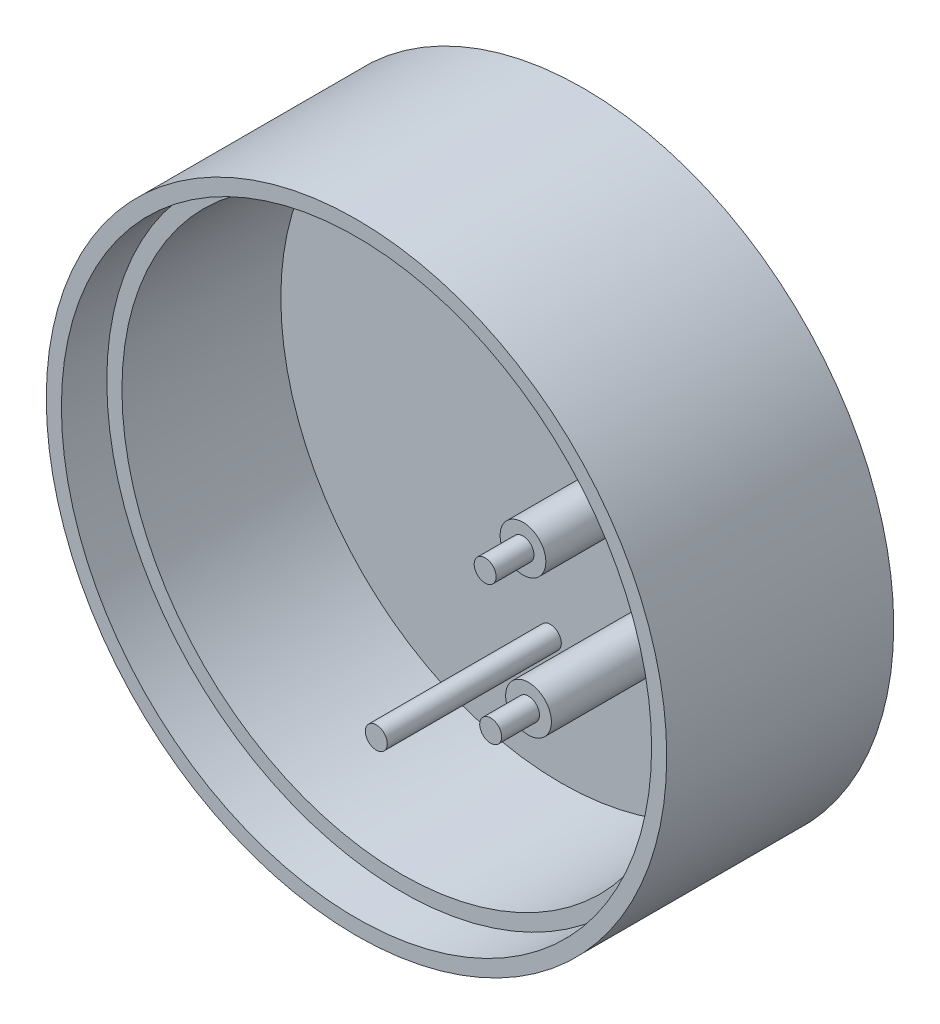
SolidWorks part; units mm, degrees
ref_plane "前视基准面" through (0, 0, 0) normal (0, 0, 1) x (1, 0, 0)
ref_plane "上视基准面" through (0, 0, 0) normal (0, 1, 0) x (1, 0, 0)
ref_plane "右视基准面" through (0, 0, 0) normal (1, 0, 0) x (0, 0, -1)
sketch "草图1" plane through (0, 0, 0) normal (0, 0, 1) x (1, 0, 0)
  circle A0 centre (0, 0) radius 41
  circle A1 centre (0, 0) radius 39
  dimension "D1" = 82
  dimension "D2" = 78
extrude "凸台-拉伸1" add sketch "草图1" along normal blind 30 contours A0 A1 region at (-39.8403, 0, 0)
sketch "草图2" plane through (0, 0, 0) normal (0, 0, 1) x (1, 0, 0)
  circle A0 centre (0, 0) radius 37
  circle A1 centre (0, 0) radius 39
  dimension "D1" = 74
  dimension "D2" = 78
extrude "凸台-拉伸2" add sketch "草图2" along normal blind 24 contours A0 | A1
sketch "草图4" plane through (0, 0, 0) normal (1, 0, 0) x (0, 0, -1)
  line L0 (-107.3488, 0) -> (127.1213, 0) construction
sketch3d "3D草图1"
  circle A1 centre (0, 0, 0) radius 39
  point P5 (0, 0, 39)
extrude "凸台-拉伸3" add sketch "3D草图1" along direction (0, 0, -1) on the side against the normal blind 3
sketch "草图5" plane through (0, 0, 3) normal (0, 0, 1) x (1, 0, 0)
  circle A0 centre (-1.3825, -21) radius 1.45
  circle A1 centre (0, 0) radius 37 construction
  dimension "D1" = 2.9
  dimension "D2" = 21
extrude "凸台-拉伸4" add sketch "草图5" along normal blind 23
sketch "草图6" plane through (0, 0, 3) normal (0, 0, 1) x (1, 0, 0)
  circle A0 centre (15.7328, -10.6527) radius 1.45
  circle A2 centre (-1.3825, -21) radius 1.45 construction
  dimension "D1" = 20
  dimension "D2" = 2.9
  dimension "D3" = 19
extrude "凸台-拉伸5" add sketch "草图6" along normal blind 25
sketch "草图7" plane through (0, 0, 3) normal (0, 0, 1) x (1, 0, 0)
  circle A0 centre (15.7328, -10.6527) radius 3.0225
extrude "凸台-拉伸6" add sketch "草图7" along normal blind 20
sketch "草图8" plane through (0, 0, 3) normal (0, 0, 1) x (1, 0, 0)
  circle A0 centre (17, 9.3071) radius 1.45
  circle A3 centre (15.7328, -10.6527) radius 3.0225 construction
  dimension "D1" = 20
  dimension "D2" = 2.9
  dimension "D3" = 17
extrude "凸台-拉伸7" add sketch "草图8" along normal blind 27
sketch "草图9" plane through (0, 0, 3) normal (0, 0, 1) x (1, 0, 0)
  circle A0 centre (17, 9.3071) radius 3.0225
  circle A1 centre (17, 9.3071) radius 1.45 construction
extrude "凸台-拉伸8" add sketch "草图9" along normal blind 22
